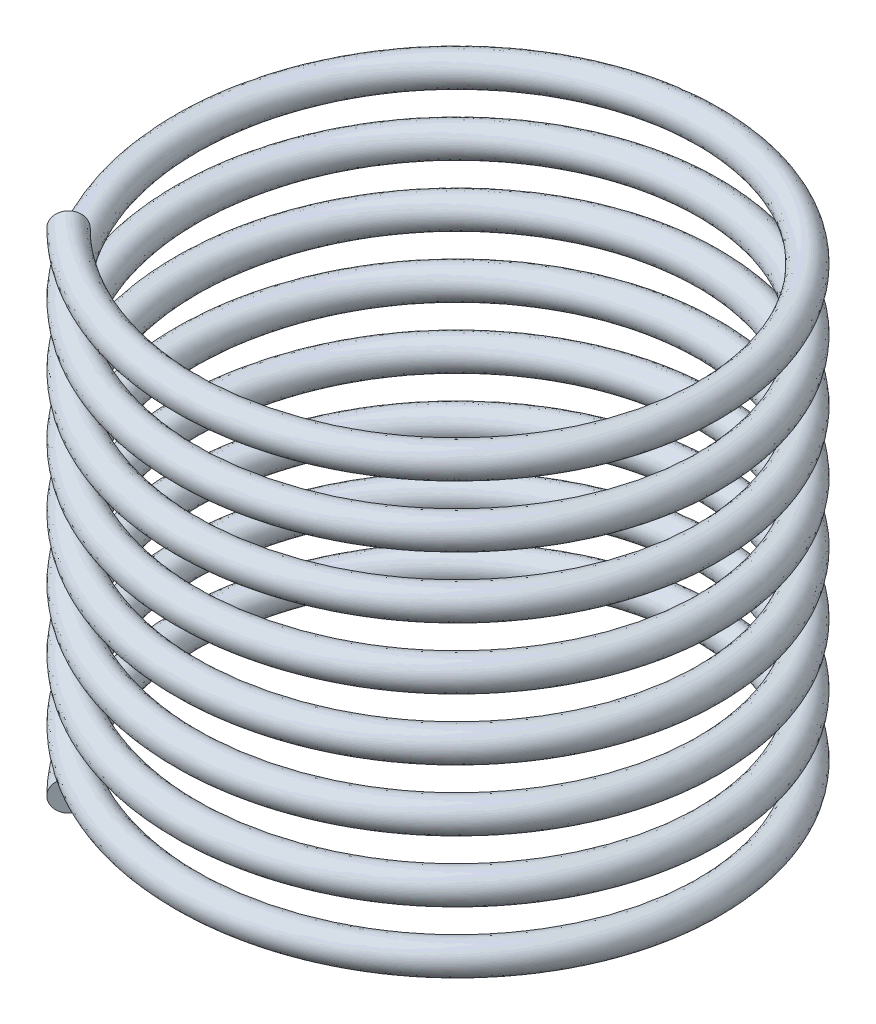
SolidWorks part; units mm, degrees
note: '?' marks a value the reader was unsure of.
ref_plane "Front Plane" through (0, 0, 0) normal (0, 0, 1) x (1, 0, 0)
ref_plane "Top Plane" through (0, 0, 0) normal (0, 1, 0) x (1, 0, 0)
ref_plane "Right Plane" through (0, 0, 0) normal (1, 0, 0) x (0, 0, -1)
sketch "Sketch1" plane through (0, 0, 0) normal (0, 1, 0) x (1, 0, 0)
  circle A0 centre (0, 0) radius 4.25
  dimension "D1" = 8.5
curve "Helix/Spiral1" pitch 1 height 8 turns 8
sweep "Sweep1" add path "Helix/Spiral1" circular profile diameter 0.5 parameters "D3"=0.5
ref_plane "Plane2" through (0, 8, 0) normal (0, 1, 0) x (1, 0, 0)
sketch "Sketch2" plane through (0, 8, 0) normal (0, 1, 0) x (1, 0, 0)
  circle A0 centre (0, 0) radius 1.0354 construction
ref_axis "Axis1" through (0, 8, 0) along (0, -1, 0)?
